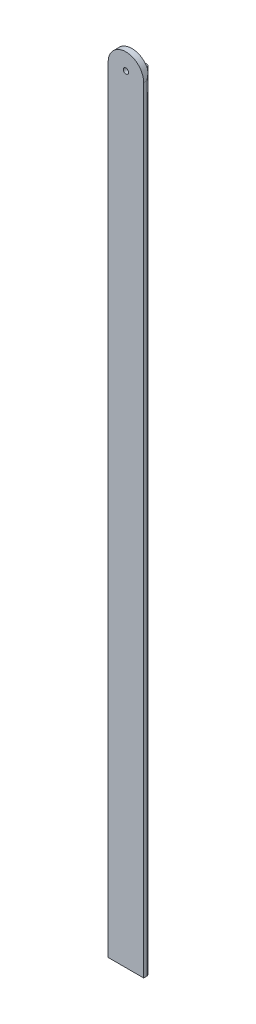
SolidWorks part; units mm, degrees
material "6061 Alloy"
ref_plane "Front Plane" through (0, 0, 0) normal (0, 0, 1) x (1, 0, 0)
ref_plane "Top Plane" through (0, 0, 0) normal (0, 1, 0) x (1, 0, 0)
ref_plane "Right Plane" through (0, 0, 0) normal (1, 0, 0) x (0, 0, -1)
sketch "Sketch2" plane through (0, 0, 0) normal (0, 1, 0) x (1, 0, 0)
  line L0 (0, 0) -> (19.05, 0)
  line L1 (0, 0) -> (0, 19.05)
  line L2 (4.7625, 3.175) -> (17.4625, 3.175)
  line L3 (3.175, 4.7625) -> (3.175, 17.4625)
  line L4 (0, 19.05) -> (1.5875, 19.05)
  line L5 (19.05, 1.5875) -> (19.05, 0)
  line L6 (3.175, 3.175) -> (3.175, 19.05) construction
  line L7 (3.175, 3.175) -> (19.05, 3.175) construction
  arc A0 (3.175, 17.4625) -> (1.5875, 19.05) centre (1.5875, 17.4625) ccw
  arc A1 (3.175, 4.7625) -> (4.7625, 3.175) centre (4.7625, 4.7625) ccw
  arc A2 (17.4625, 3.175) -> (19.05, 1.5875) centre (17.4625, 1.5875) cw
  dimension "D2" = 1.5875
  dimension "D1" = 3.175
extrude "Boss-Extrude1" add sketch "Sketch2" along normal blind 431.8
sketch "Sketch4" plane through (3.175, 0, 0) normal (1, 0, 0) x (0, 0, -1)
  line L0 (19.05, 431.8) -> (19.05, 406.4)
  line L1 (19.05, 431.8) -> (19.05, 0) construction
  line L2 (19.05, 406.4) -> (3.175, 406.4)
  line L3 (3.175, 431.8) -> (3.175, 0) construction
  line L4 (3.175, 406.4) -> (3.175, 431.8)
  line L5 (3.175, 431.8) -> (19.05, 431.8)
extrude "Cut-Extrude1" cut sketch "Sketch4" against normal blind 6.35
sketch "Sketch5" plane through (3.175, 0, 0) normal (-1, 0, 0) x (0, 0, 1)
  line L8 (-4.7625, 406.4) -> (-3.175, 406.4)
  line L9 (-3.175, 406.4) -> (-3.175, 431.8)
  line L10 (-3.175, 431.8) -> (-4.7625, 431.8)
  line L11 (-4.7625, 431.8) -> (-4.7625, 406.4)
  line L12 (-4.7625, 406.4) -> (-3.175, 406.4)
  line L13 (-3.175, 406.4) -> (-3.175, 431.8)
  line L14 (-3.175, 431.8) -> (-4.7625, 431.8)
  line L15 (-4.7625, 431.8) -> (-4.7625, 406.4)
  dimension "D1" = 0
extrude "Cut-Extrude2" cut sketch "Sketch5" against normal blind 6.35
sketch "Sketch6" plane through (3.175, 0, 0) normal (1, 0, 0) x (0, 0, -1)
  line L0 (19.05, 0) -> (3.175, 0) construction
  line L1 (11.1125, 0) -> (11.1125, 15.875) construction
  line L2 (19.05, 406.4) -> (3.175, 406.4) construction
  line L3 (11.1125, 406.4) -> (11.1125, 390.525) construction
  line L4 (11.1125, 15.875) -> (11.1125, 203.2) construction
  line L5 (11.1125, 203.2) -> (11.1125, 390.525) construction
  circle A1 centre (11.1125, 109.5375) radius 1.4224
  circle A2 centre (11.1125, 203.2) radius 1.4224
  circle A3 centre (11.1125, 296.8625) radius 1.4224
  circle A5 centre (11.1125, 11.1125) radius 1.4224
  circle A6 centre (11.1125, 395.2875) radius 1.4224
  point P12 (11.1125, 203.2)
  point P13 (11.1125, 296.8625)
  point P15 (11.1125, 109.5375)
  dimension "D2" = 2.8448
  dimension "D3" = 2.8448
  dimension "D4" = 2.8448
  dimension "D6" = 2.8448
  dimension "D7" = 2.8448
extrude "Cut-Extrude3" cut sketch "Sketch6" against normal blind 5.08
sketch "Sketch7" plane through (0, 431.8, 0) normal (0, 1, 0) x (1, 0, 0)
  line L8 (17.4625, 3.175) -> (0, 3.175)
  line L9 (0, 3.175) -> (0, 0)
  line L10 (0, 0) -> (19.05, 0)
  line L11 (19.05, 0) -> (19.05, 1.5875)
  line L12 (17.4625, 3.175) -> (0, 3.175)
  line L13 (0, 3.175) -> (0, 0)
  line L14 (0, 0) -> (19.05, 0)
  line L15 (19.05, 0) -> (19.05, 1.5875)
  arc A2 (19.05, 1.5875) -> (17.4625, 3.175) centre (17.4625, 1.5875) ccw
  arc A3 (19.05, 1.5875) -> (17.4625, 3.175) centre (17.4625, 1.5875) ccw
  dimension "D1" = 0
extrude "Cut-Extrude4" cut sketch "Sketch7" against normal blind 6.35
sketch "Sketch8" plane through (0, 0, -3.175) normal (0, 0, -1) x (-1, 0, 0)
  line L0 (0, 425.45) -> (0, 416.56) construction
  line L1 (0, 425.45) -> (0, 406.4) construction
  line L2 (0, 416.56) -> (-9.525, 416.56) construction
  circle A0 centre (-9.525, 416.56) radius 1.4224
  dimension "D1" = 2.8448
extrude "Cut-Extrude5" cut sketch "Sketch8" against normal blind 5.08
ref_plane "Plane1" through (0, 0, 2.54) normal (0, 0, 1) x (1, 0, 0)
sketch "Sketch10" plane through (0, 0, -3.175) normal (0, 0, -1) x (-1, 0, 0)
  line L0 (-9.525, 416.56) -> (-9.525, 415.925) construction
  line L3 (-19.05, 415.925) -> (-19.05, 425.45)
  line L4 (-19.05, 425.45) -> (0, 425.45)
  line L5 (0, 415.925) -> (0, 425.45)
  line L7 (-19.05, 425.45) -> (-16.2602, 422.6602) construction
  line L8 (-2.7898, 422.6602) -> (0, 425.45) construction
  arc A0 (0, 415.925) -> (-19.05, 415.925) centre (-9.525, 415.925) ccw
  line M3 (0, 425.45) -> (-17.4625, 425.45)
  line M4 (-17.4625, 425.45) -> (-17.4625, 0)
  line M8 (0, 406.4) -> (0, 425.45)
extrude "Cut-Extrude7" cut sketch "Sketch10" against normal blind 5.08 contours A0 M8 M3 | A0 L4 M4 | A0 L4 L3 M4 region at (2.1276, 423.3224, -3.175) region at (18.3487, 422.3469, -3.175) region at (15.5776, 424.2422, -3.175)
